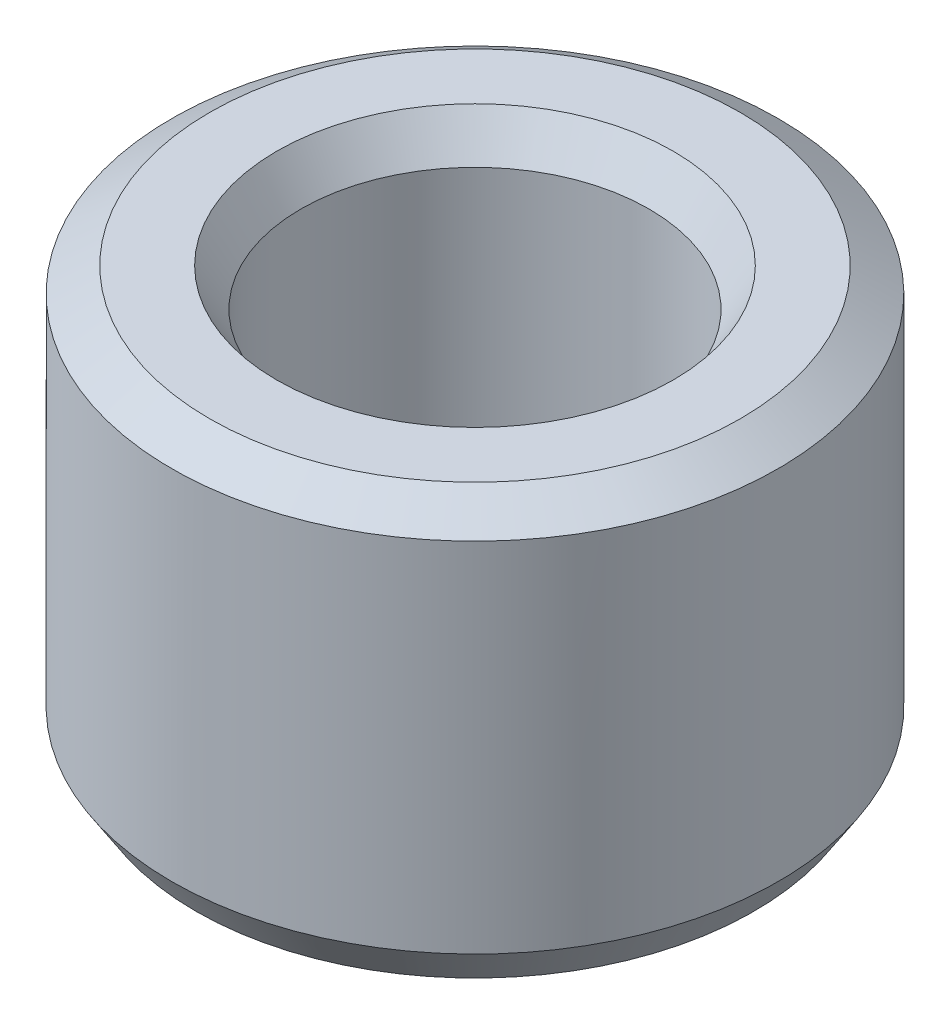
SolidWorks part; units mm, degrees
ref_plane "Front Plane" through (0, 0, 0) normal (0, 0, 1) x (1, 0, 0)
ref_plane "Top Plane" through (0, 0, 0) normal (0, 1, 0) x (1, 0, 0)
ref_plane "Right Plane" through (0, 0, 0) normal (1, 0, 0) x (0, 0, -1)
sketch "Sketch1" plane through (0, 0, 0) normal (0, 1, 0) x (1, 0, 0)
  circle A0 centre (0, 0) radius 37.5
  dimension "SLEEVE_OD" = 75
extrude "Boss-Extrude1" add sketch "Sketch1" along normal blind 51.9073
sketch "Sketch2" plane through (0, 0, 0) normal (0, 1, 0) x (1, 0, 0)
  circle A0 centre (0, 0) radius 21.5174
  dimension "BORE_D" = 43.0348
extrude "Cut-Extrude1" cut sketch "Sketch2" along normal through all
chamfer "Chamfer1" distance 2.9984 angle 57.397 4 edges at (0, 51.9073, 21.5174) (0, 0, 21.5174) (0, 0, 37.5) (0, 51.9073, 37.5) first distance on face at (0, 51.9073, 21.5174) first distance on face at (0, 0, 21.5174) first distance on face at (0, 51.9073, 37.5)
